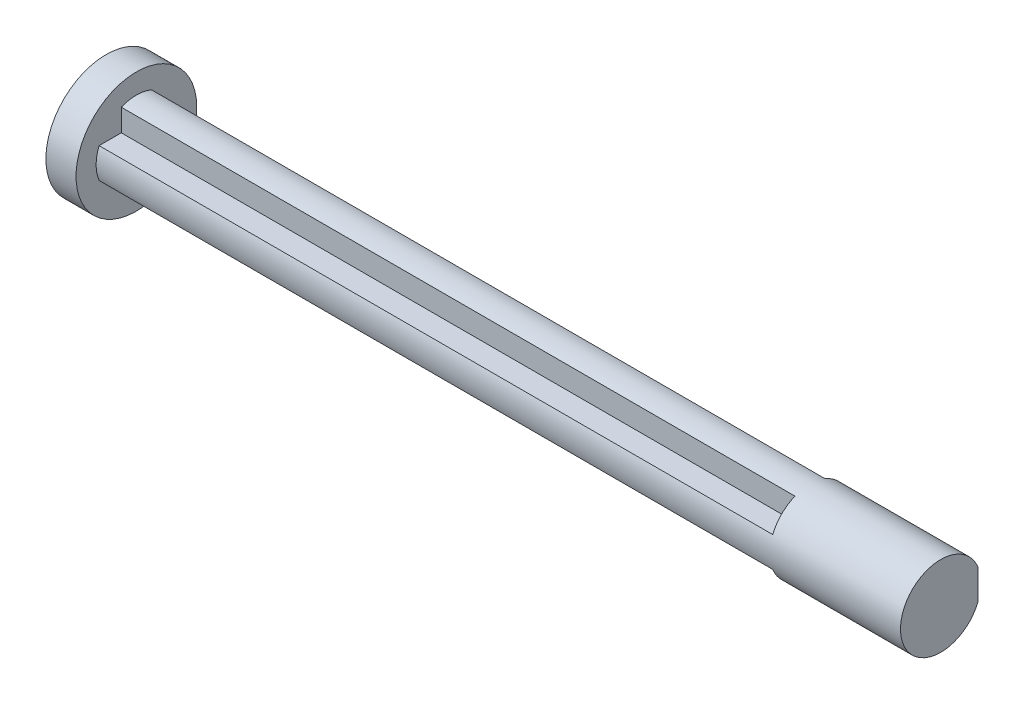
SolidWorks part; units mm, degrees
ref_plane "Front Plane" through (0, 0, 0) normal (0, 0, 1) x (1, 0, 0)
ref_plane "Top Plane" through (0, 0, 0) normal (0, 1, 0) x (1, 0, 0)
ref_plane "Right Plane" through (0, 0, 0) normal (1, 0, 0) x (0, 0, -1)
sketch "Sketch2" plane through (0, 0, 0) normal (1, 0, 0) x (0, 0, -1)
  line L0 (-1.5, 3.7081) -> (-1.5, 1.5)
  line L1 (1.5, 3.7081) -> (1.5, 1.5)
  line L2 (0, 0) -> (0, 12.4074) construction
  line L3 (3.7081, -1.5) -> (1.5, -1.5)
  line L4 (3.7081, 1.5) -> (1.5, 1.5)
  line L5 (-1.5, -3.7081) -> (-1.5, -1.5)
  line L6 (1.5, -3.7081) -> (1.5, -1.5)
  line L7 (-3.7081, 1.5) -> (-1.5, 1.5)
  line L8 (-3.7081, -1.5) -> (-1.5, -1.5)
  circle A0 centre (0, 0) radius 6
  arc A1 (-1.5, 3.7081) -> (1.5, 3.7081) centre (0, 0) cw
  arc A2 (3.7081, 1.5) -> (3.7081, -1.5) centre (0, 0) cw
  arc A3 (1.5, -3.7081) -> (-1.5, -3.7081) centre (0, 0) cw
  arc A4 (-3.7081, -1.5) -> (-3.7081, 1.5) centre (0, 0) cw
  point P8 (0, 0)
  point P10 (0, 0)
  point P24 (0, 0)
  dimension "D1" = 12
  dimension "D2" = 4
  dimension "D3" = 3
  dimension "D4" = 1.5
  dimension "D5" = 4
extrude "Boss-Extrude2" add sketch "Sketch2" along normal blind 67 contours L2 A3 L6 L3 A2 L4 L1 A1 | A3 L2 A1 L0 L7 A4 L8 L5 region at (0, 3.8153, 0.7425)
extrude "Boss-Extrude3" add sketch "Sketch2<4>" against normal blind 3 contours L2 A0 A1 L1 L4 A2 L3 L6 A3 | L2 A3 L6 L3 A2 L4 L1 A1 | A3 L2 A1 L0 L7 A4 L8 L5 | A0 L2 A3 L5 L8 A4 L7 L0 A1 region at (0, 3.8153, 0.7425) region at (0, 4.1226, -4.1226)
sketch "Sketch2<4>" plane through (0, 0, 0) normal (1, 0, 0) x (0, 0, -1) same geometry as "Sketch2"
sketch "Sketch4" plane through (67, 0, 0) normal (1, 0, 0) x (0, 0, -1)
  circle A0 centre (0, 0) radius 4
extrude "Boss-Extrude5" add sketch "Sketch4" along normal blind 2
sketch "Sketch7" plane through (69, 0, 0) normal (1, 0, 0) x (0, 0, -1)
  line L0 (-3.7081, 1.5) -> (-3.7081, -1.5)
  line L1 (3.7081, 1.5) -> (3.7081, -1.5)
  arc A0 (-3.7081, 1.5) -> (3.7081, 1.5) centre (0, 0) cw
  circle A1 centre (0, 0) radius 4 construction
  arc A2 (-3.7081, -1.5) -> (3.7081, -1.5) centre (0, 0) ccw
  point P8 (0, 0)
  point P9 (0, 0)
  circle M5 centre (0, 0) radius 4
  dimension "D1" = 3
  dimension "D2" = 3
extrude "Boss-Extrude6" add sketch "Sketch7" along normal blind 11
sketch "Sketch8" plane through (0, 0, -3.7081) normal (0, 0, -1) x (-1, 0, 0)
  line L0 (-80, -1.5) -> (-80, 1.5) construction
  line L1 (-80, -4) -> (0, -4) construction
  circle A0 centre (-75, 0) radius 1.5
  dimension "D1" = 3
  dimension "D2" = 5
  dimension "D3" = 4
extrude "Cut-Extrude1" cut sketch "Sketch8" against normal blind 4
extrude "Boss-Extrude7" add sketch "Sketch7<2>" along normal blind 11 contours L0 M5 region at (69, 0, 3.8252)
sketch "Sketch7<2>" plane through (69, 0, 0) normal (1, 0, 0) x (0, 0, -1) same geometry as "Sketch7"
